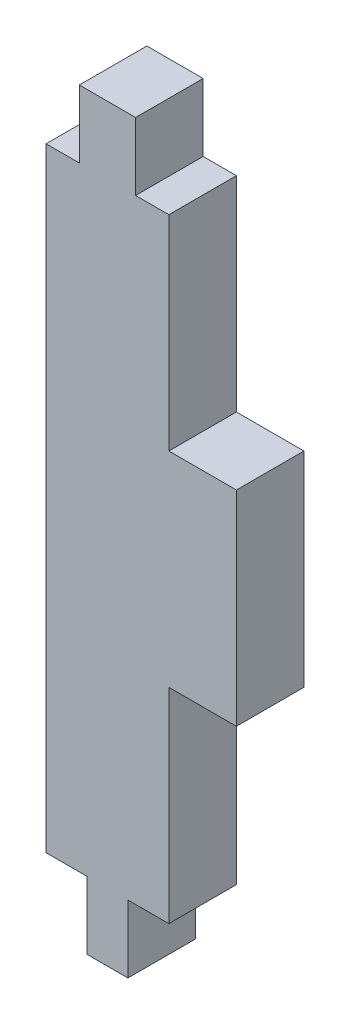
SolidWorks part; units mm, degrees
ref_plane "Front Plane" through (0, 0, 0) normal (0, 0, 1) x (1, 0, 0)
ref_plane "Top Plane" through (0, 0, 0) normal (0, 1, 0) x (1, 0, 0)
ref_plane "Right Plane" through (0, 0, 0) normal (1, 0, 0) x (0, 0, -1)
sketch "Sketch1" plane through (0, 0, 0) normal (0, 0, 1) x (1, 0, 0)
  line L0 (-34.5223, -10.68) -> (-29.9389, -10.68)
  line L1 (-37.2306, -16.18) -> (-27.2306, -16.18)
  line L2 (-37.2306, -16.18) -> (-37.2306, -66.18)
  line L3 (-37.2306, -66.18) -> (-27.2306, -66.18)
  line L4 (-27.2306, -16.18) -> (-27.2306, -66.18)
  line L5 (-37.2306, -16.18) -> (-27.2306, -66.18) construction
  line L6 (-37.2306, -66.18) -> (-27.2306, -16.18) construction
  line L7 (-33.8973, -60.68) -> (-30.5639, -60.68)
  line L8 (-33.8973, -60.68) -> (-33.8973, -71.68)
  line L9 (-33.8973, -71.68) -> (-30.5639, -71.68)
  line L10 (-30.5639, -60.68) -> (-30.5639, -71.68)
  line L11 (-33.8973, -60.68) -> (-30.5639, -71.68) construction
  line L12 (-33.8973, -71.68) -> (-30.5639, -60.68) construction
  line L13 (-34.5223, -10.68) -> (-34.5223, -21.68)
  line L14 (-34.5223, -21.68) -> (-29.9389, -21.68)
  line L15 (-29.9389, -10.68) -> (-29.9389, -21.68)
  line L16 (-34.5223, -10.68) -> (-29.9389, -21.68) construction
  line L17 (-34.5223, -21.68) -> (-29.9389, -10.68) construction
  line L19 (-27.2306, -49.5133) -> (-21.7306, -49.5133)
  line L20 (-27.2306, -49.5133) -> (-27.2306, -32.8467)
  line L21 (-27.2306, -32.8467) -> (-21.7306, -32.8467)
  line L22 (-21.7306, -49.5133) -> (-21.7306, -32.8467)
  point P0 (-32.2306, -41.18)
  point P5 (-32.2306, -66.18)
  point P10 (-32.2306, -16.18)
  dimension "D1" = 50
  dimension "D2" = 10
  dimension "D3" = 5.5
  dimension "D4" = 1.6667
  dimension "D5" = 16.6667
  dimension "D6" = 16.6667
  dimension "D7" = 5.5
  dimension "D8" = 5.5
extrude "Boss-Extrude1" add sketch "Sketch1" along normal blind 5.5 contours L1 L4 L3 L2 | L13 L14 L15 L0 | L10 L9 L8 L7 | L22 L21 L20 L19
equation "\"mat\"=\"mat@V1.assembly\""
equation "\"D3@Sketch1\"=\"mat\""
equation "\"D4@Sketch1\" = 10/6"
equation "\"D1@Boss-Extrude1\"=\"mat\""
equation "\"D7@Sketch1\" = \"mat\""
equation "\"D8@Sketch1\" = \"mat\""
